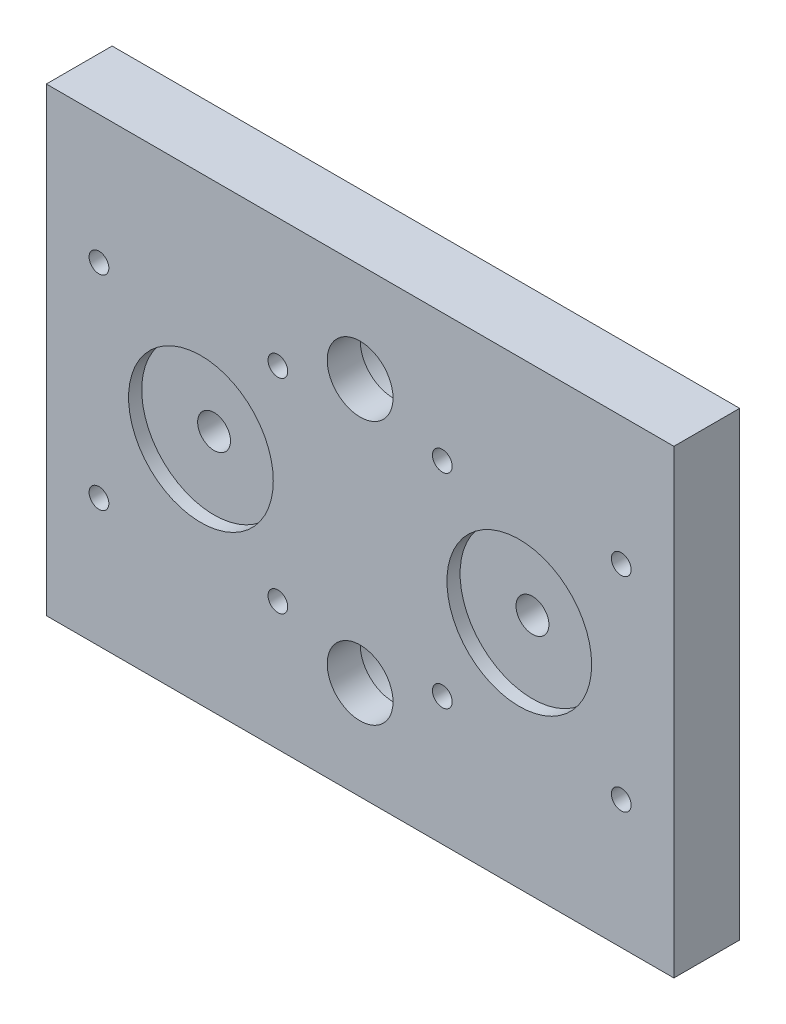
SolidWorks part; units mm, degrees
ref_plane "Front Plane" through (0, 0, 0) normal (0, 0, 1) x (1, 0, 0)
ref_plane "Top Plane" through (0, 0, 0) normal (0, 1, 0) x (1, 0, 0)
ref_plane "Right Plane" through (0, 0, 0) normal (1, 0, 0) x (0, 0, -1)
sketch "Sketch1" plane through (0, 0, 0) normal (0, 0, 1) x (1, 0, 0)
  line L0 (0, 0) -> (0, 40) construction
  line L2 (12.5, -15) -> (-12.5, -15)
  line L3 (12.5, -15) -> (12.5, 55)
  line L4 (12.5, 55) -> (-12.5, 55)
  line L5 (-12.5, -15) -> (-12.5, 55)
  line L6 (12.5, -15) -> (-12.5, 55) construction
  line L7 (12.5, 55) -> (-12.5, -15) construction
  circle A0 centre (0, 40) radius 7.9375
  circle A1 centre (0, 0) radius 7.9375
  point P5 (0, 20)
  dimension "D2" = 15.875
  dimension "D1" = 40
  dimension "D3" = 70
  dimension "D4" = 25
extrude "Boss-Extrude1" add sketch "Sketch1" along normal blind 10
sketch "Sketch2" plane through (0, 0, 10) normal (0, 0, 1) x (1, 0, 0)
  line L0 (12.5, 55) -> (-12.5, 55) construction
  line L1 (-47.7, 55) -> (-8.2, 55)
  line L3 (-47.7, -15) -> (-8.2, -15)
  line L4 (-8.2, 55) -> (-8.2, 36.9142)
  line L5 (-39.7, 35.5) -> (-8.7, 4.5) construction
  line L6 (-39.7, 4.5) -> (-8.7, 35.5) construction
  line L7 (-12.5, -15) -> (12.5, -15) construction
  line L8 (-8.2, 34.0858) -> (-8.2, 5.9142)
  line L9 (0, 55) -> (0, -15) construction
  line L10 (-8.7, 4.5) -> (-39.7, 4.5) construction
  line L11 (-8.7, 4.5) -> (-8.7, 35.5) construction
  line L12 (-8.7, 35.5) -> (-39.7, 35.5) construction
  line L13 (-39.7, 4.5) -> (-39.7, 35.5) construction
  line L14 (-8.7, 4.5) -> (-39.7, 35.5) construction
  line L15 (-8.7, 35.5) -> (-39.7, 4.5) construction
  line L16 (8.7, 35.5) -> (39.7, 4.5) construction
  line L17 (8.7, 4.5) -> (39.7, 35.5) construction
  line L18 (39.7, 4.5) -> (39.7, 35.5) construction
  line L19 (8.7, 35.5) -> (39.7, 35.5) construction
  line L20 (8.7, 4.5) -> (8.7, 35.5) construction
  line L21 (8.7, 4.5) -> (39.7, 4.5) construction
  line L22 (39.7, 4.5) -> (8.7, 35.5) construction
  line L23 (39.7, 35.5) -> (8.7, 4.5) construction
  line L24 (8.2, 55) -> (8.2, 36.9142)
  line L25 (47.7, -15) -> (8.2, -15)
  line L27 (47.7, 55) -> (8.2, 55)
  line L28 (-47.7, 55) -> (-47.7, -15)
  line L29 (47.7, 55) -> (47.7, -15)
  line L31 (-8.2, 3.0858) -> (-8.2, -15)
  line L32 (8.2, 3.0858) -> (8.2, -15)
  line L33 (8.2, 34.0858) -> (8.2, 5.9142)
  circle A0 centre (-39.7, 35.5) radius 1.5
  arc A1 (-8.2, 36.9142) -> (-8.2, 34.0858) centre (-8.7, 35.5) ccw
  arc A2 (-8.2, 5.9142) -> (-8.2, 3.0858) centre (-8.7, 4.5) ccw
  circle A3 centre (-39.7, 4.5) radius 1.5
  circle A4 centre (39.7, 4.5) radius 1.5
  arc A5 (8.2, 5.9142) -> (8.2, 3.0858) centre (8.7, 4.5) cw
  arc A6 (8.2, 36.9142) -> (8.2, 34.0858) centre (8.7, 35.5) cw
  circle A7 centre (39.7, 35.5) radius 1.5
  circle A8 centre (-24.2, 20) radius 2.5
  circle A9 centre (24.2, 20) radius 2.5
  point P0 (-24.2, 20)
  point P11 (-24.2, 20)
  point P34 (24.2, 20)
  dimension "D2" = 3
  dimension "D3" = 5
  dimension "D1" = 31
  dimension "D4" = 0.5
  dimension "D5" = 8
  dimension "D6" = 8.2
extrude "Boss-Extrude2" add sketch "Sketch2" against normal up to surface (10 mm away) up to face at (0, 20, 0)
sketch "Sketch6" plane through (0, 0, 10) normal (0, 0, 1) x (1, 0, 0)
  circle A0 centre (-12.5, 35.5) radius 1.5
  circle A1 centre (12.5, 35.5) radius 1.5
  circle A2 centre (-12.5, 4.5) radius 1.5
  circle A3 centre (12.5, 4.5) radius 1.5
  circle A5 centre (-39.7, 35.5) radius 1.5 construction
  point P19 (0, 0)
extrude "Cut-Extrude3" cut sketch "Sketch6" against normal up to surface (10 mm away) up to face at (0, 20, 0)
sketch "Sketch3" plane through (0, 0, 10) normal (0, 0, 1) x (1, 0, 0)
  circle A0 centre (0, 40) radius 7.9375
  circle A1 centre (0, 0) radius 7.9375
  circle A2 centre (0, 40) radius 7.9375 construction
  circle A3 centre (0, 40) radius 5
  circle A4 centre (0, 0) radius 5
  dimension "D1" = 10
extrude "Boss-Extrude3" add sketch "Sketch3" against normal blind 5.0216
sketch "Sketch4" plane through (0, 0, 10) normal (0, 0, 1) x (1, 0, 0)
  circle A0 centre (-24.2, 20) radius 11
  circle A1 centre (24.2, 20) radius 11
  dimension "D1" = 22
extrude "Cut-Extrude1" cut sketch "Sketch4" against normal blind 2
sketch "Sketch5" plane through (0, 0, 0) normal (0, 0, -1) x (-1, 0, 0)
  circle A0 centre (-39.7, 35.5) radius 2.75
  circle A1 centre (-12.5, 35.5) radius 2.75
  circle A2 centre (-39.7, 4.5) radius 2.75
  circle A3 centre (-12.5, 4.5) radius 2.75
  circle A4 centre (12.5, 35.5) radius 2.75
  circle A5 centre (39.7, 35.5) radius 2.75
  circle A6 centre (12.5, 4.5) radius 2.75
  circle A7 centre (39.7, 4.5) radius 2.75
  circle A9 centre (12.5, 4.5) radius 1.5 construction
  circle A10 centre (-12.5, 4.5) radius 1.5 construction
  circle A11 centre (-12.5, 35.5) radius 1.5 construction
  circle A12 centre (12.5, 35.5) radius 1.5 construction
  point P14 (-12.5, 2.0024)
  point P24 (0, 0)
  point P25 (13.1353, 3.2304)
  point P27 (-9.775, 32.8938)
  point P30 (16.5784, 34)
  dimension "D1" = 5.5
extrude "Cut-Extrude2" cut sketch "Sketch5" against normal blind 3.1
